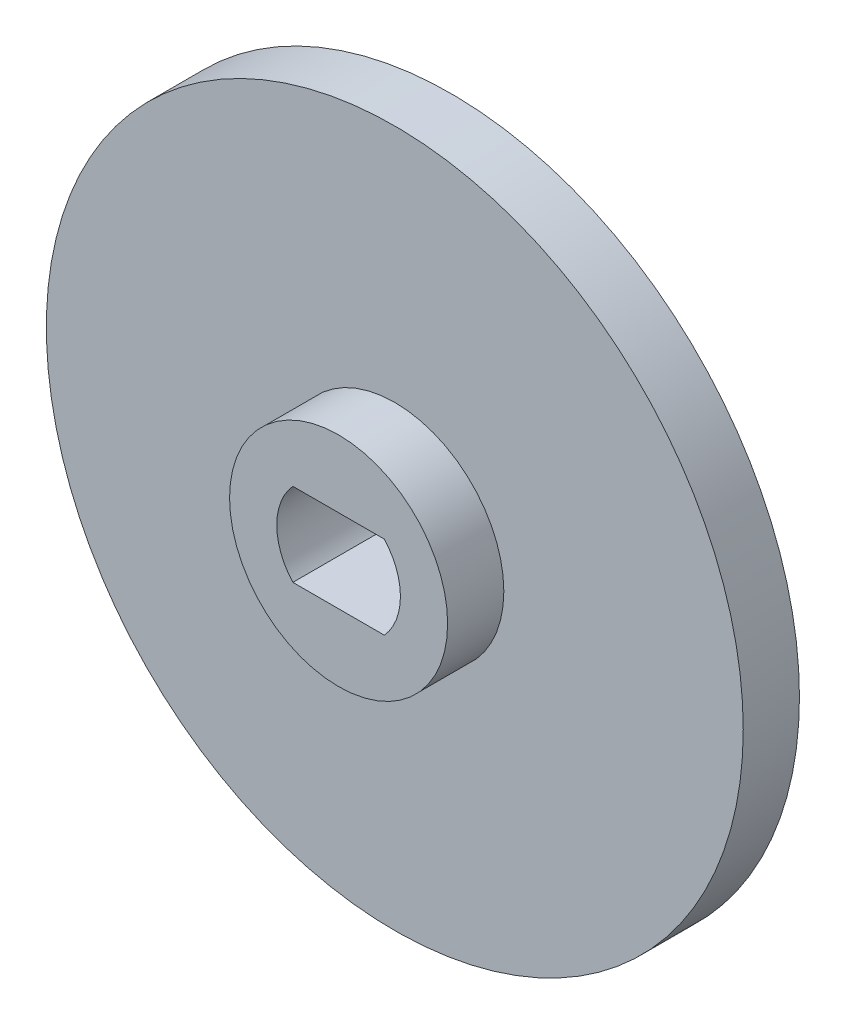
SolidWorks part; units mm, degrees
ref_plane "Front Plane" through (0, 0, 0) normal (0, 0, 1) x (1, 0, 0)
ref_plane "Top Plane" through (0, 0, 0) normal (0, 1, 0) x (1, 0, 0)
ref_plane "Right Plane" through (0, 0, 0) normal (1, 0, 0) x (0, 0, -1)
sketch "Sketch1" plane through (0, 0, 0) normal (0, 0, 1) x (1, 0, 0)
  circle A0 centre (0, 0) radius 15.5 construction
  circle A1 centre (0, 0) radius 15.5
extrude "Boss-Extrude1" add sketch "Sketch1" along normal blind 2.5
sketch "Sketch2" plane through (0, 0, 0) normal (0, 0, -1) x (-1, 0, 0)
  line L0 (-7.8174, 8.129) -> (-3.5527, 4.927)
  line L1 (0.2749, 6.0681) -> (2.0901, 11.0826)
  line L2 (-7.8774, 8.0491) -> (-3.6127, 4.8471)
  line L3 (0.3689, 6.0341) -> (2.1842, 11.0485)
  line L4 (-7.8774, 8.0491) -> (-3.6127, 4.8471) construction
  line L5 (0.3689, 6.0341) -> (2.1842, 11.0485) construction
  arc A0 (1.3416, 12.2836) -> (-7.8486, 9.5439) centre (0, 0) ccw
  arc A1 (-7.8486, 9.5439) -> (-7.8174, 8.129) centre (-7.277, 8.8488) ccw
  arc A2 (-3.5527, 4.927) -> (-2.5887, 4.8527) centre (-3.0123, 5.6468) ccw
  arc A3 (-0.491, 5.478) -> (-2.5887, 4.8527) centre (0, 0) ccw
  arc A4 (-0.491, 5.478) -> (0.2749, 6.0681) centre (-0.5714, 6.3744) ccw
  arc A5 (2.0901, 11.0826) -> (1.3416, 12.2836) centre (1.2439, 11.3889) ccw
  arc A6 (1.3524, 12.383) -> (-7.9122, 9.6211) centre (0, 0) ccw
  arc A7 (-7.9122, 9.6211) -> (-7.8774, 8.0491) centre (-7.277, 8.8488) ccw
  arc A8 (-3.6127, 4.8471) -> (-2.5416, 4.7645) centre (-3.0123, 5.6468) ccw
  arc A9 (-0.4821, 5.3784) -> (-2.5416, 4.7645) centre (0, 0) ccw
  arc A10 (-0.4821, 5.3784) -> (0.3689, 6.0341) centre (-0.5714, 6.3744) ccw
  arc A11 (2.1842, 11.0485) -> (1.3524, 12.383) centre (1.2439, 11.3889) ccw
  arc A12 (1.3524, 12.383) -> (-7.9122, 9.6211) centre (0, 0) ccw construction
  arc A13 (-7.9122, 9.6211) -> (-7.8774, 8.0491) centre (-7.277, 8.8488) ccw construction
  arc A14 (-3.6127, 4.8471) -> (-2.5416, 4.7645) centre (-3.0123, 5.6468) ccw construction
  arc A15 (-0.4821, 5.3784) -> (-2.5416, 4.7645) centre (0, 0) ccw construction
  arc A16 (-0.4821, 5.3784) -> (0.3689, 6.0341) centre (-0.5714, 6.3744) ccw construction
  arc A17 (2.1842, 11.0485) -> (1.3524, 12.383) centre (1.2439, 11.3889) ccw construction
  dimension "D1" = 0
  dimension "D2" = 0.1
extrude "Boss-Extrude2" add sketch "Sketch2" along normal offset from surface (1.9 mm away) 0.3
pattern_circular "CirPattern1" count 5 over 360 about axis through (0, 0, 2.5) along (0, 0, -1) of "Boss-Extrude2"
sketch "Sketch3" plane through (0, 0, 0) normal (0, 0, 1) x (1, 0, 0)
  circle A0 centre (0, 0) radius 4.85
  dimension "D1" = 9.7
extrude "Boss-Extrude3" add sketch "Sketch3" along normal blind 2.5 from surface starting at face at (15.5, 0, 2.5)
sketch "Sketch4" plane through (0, 0, 0) normal (0, 0, 1) x (1, 0, 0)
  circle A0 centre (0, 0) radius 2
  dimension "D1" = 4
extrude "Cut-Extrude1" [suppressed] cut sketch "Sketch4" along normal through all
sketch "Sketch5" plane through (0, 0, 5) normal (0, 0, 1) x (1, 0, 0)
  line L0 (-2.0347, 1.85) -> (2.0347, 1.85)
  line L1 (2.0347, -1.85) -> (-2.0347, -1.85)
  arc A0 (-2.0347, 1.85) -> (-2.0347, -1.85) centre (0, 0) ccw
  arc A1 (2.0347, -1.85) -> (2.0347, 1.85) centre (0, 0) ccw
  dimension "D1" = 5.5
  dimension "D2" = 3.7
extrude "Cut-Extrude2" cut sketch "Sketch5" against normal through all
sketch "Sketch6" plane through (0, 0, 0) normal (0, 0, -1) x (-1, 0, 0)
  circle A1 centre (0, 0) radius 15.5 construction
  circle A2 centre (0, 0) radius 15.5
  circle A3 centre (0, 0) radius 13.5
  dimension "D1" = 2
extrude "Boss-Extrude4" [suppressed] add sketch "Sketch6" along normal offset from surface (0.9 mm away) 0.1
